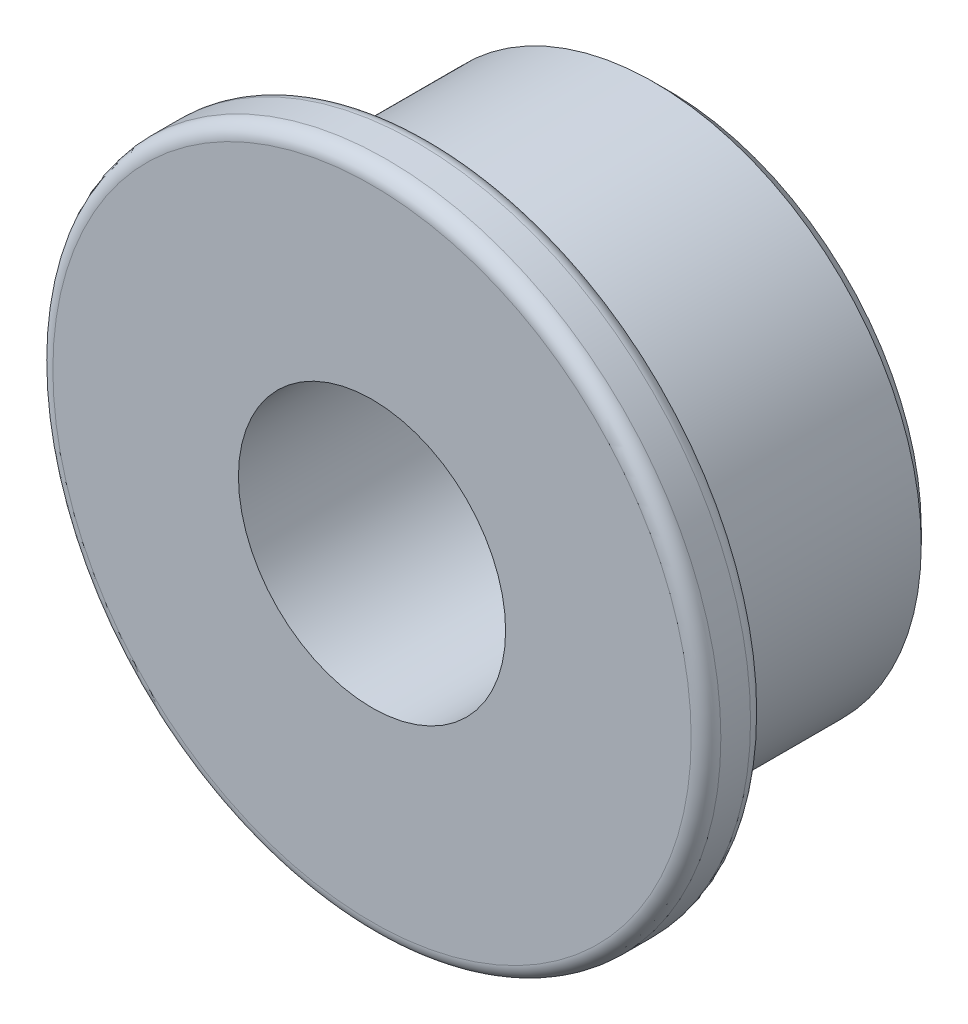
SolidWorks part; units mm, degrees
ref_plane "Front Plane" through (0, 0, 0) normal (0, 0, 1) x (1, 0, 0)
ref_plane "Top Plane" through (0, 0, 0) normal (0, 1, 0) x (1, 0, 0)
ref_plane "Right Plane" through (0, 0, 0) normal (1, 0, 0) x (0, 0, -1)
sketch "Sketch1" plane through (0, 0, 0) normal (0, 0, 1) x (1, 0, 0)
  circle A0 centre (0, 0) radius 9
  circle A1 centre (0, 0) radius 4.5
  dimension "D1" = 18
  dimension "D2" = 9
extrude "Boss-Extrude1" add sketch "Sketch1" against normal blind 8
sketch "Sketch2" plane through (0, 0, 0) normal (0, 0, 1) x (1, 0, 0)
  circle A0 centre (0, 0) radius 11.25
  circle A1 centre (0, 0) radius 4.5
  circle A2 centre (0, 0) radius 4.5 construction
  dimension "D1" = 22.5
extrude "Boss-Extrude2" add sketch "Sketch2" along normal blind 2
fillet "Fillet1" radius 0.5 1 edges at (11.25, 0, 2)
fillet "Fillet2" radius 0.5 1 edges at (11.25, 0, 0)
fillet "Fillet3" radius 0.8 1 edges at (9, 0, 0)
chamfer "Chamfer1" distance 0.5 angle 45 1 edges at (9, 0, -8)
